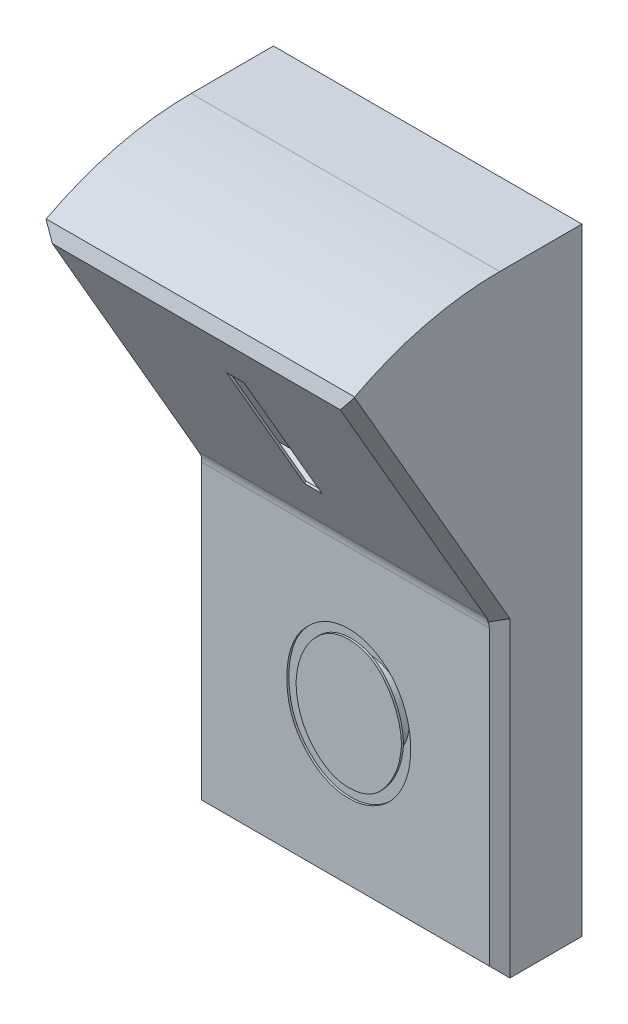
SolidWorks part; units mm, degrees
ref_plane "Plano frontal" through (0, 0, 0) normal (0, 0, 1) x (1, 0, 0)
ref_plane "Plano superior" through (0, 0, 0) normal (0, 1, 0) x (1, 0, 0)
ref_plane "Plano direito" through (0, 0, 0) normal (1, 0, 0) x (0, 0, -1)
sketch "Esboço1" plane through (0, 0, 0) normal (1, 0, 0) x (0, 0, -1)
  line L0 (0, 0) -> (0, 30)
  line L1 (0, 30) -> (-3.9988, 30)
  line L2 (0, 0) -> (-4, 0)
  line L3 (-4, 0) -> (-4, 15)
  line L6 (-11.5, 27.99) -> (-4, 15)
  arc A0 (-11.5, 27.99) -> (-3.9988, 30) centre (-3.9988, 14.9979) cw
extrude "Ressalto-extrusão1" add sketch "Esboço1" along normal blind 15
chamfer "Chanfro1" distance 0.5 angle 45 6 edges at (15, 21.495, 7.75) (7.5, 27.99, 11.5) (0, 21.495, 7.75) (0, 7.5, 4) (7.5, 0, 4) (15, 7.5, 4)
fillet "Filete1" radius 1 1 edges at (7.5, 15, 4)
sketch "Esboço2" plane through (0, 2.0181, -3.4953) normal (0, -0.5, 0.866) x (1, 0, 0)
  text T0 "l" font "Ebrima" height in points 28
sketch "Esboço4" plane through (0, 0, 4) normal (0, 0, 1) x (1, 0, 0)
  text T0 "O" font "Courier New" height in points 32
extrude "Corte-extrusão1" cut sketch "Esboço4" against normal blind 0.1
extrude "Corte-extrusão2" cut sketch "Esboço2" against normal blind 0.1
ref_plane "Plano1" through (0, 2.0681, -3.5819) normal (0, -0.5, 0.866) x (1, 0, 0)
sketch "Esboço5" plane through (0, 2.0681, -3.5819) normal (0, -0.5, 0.866) x (1, 0, 0)
  line L1 (12.5, 17.6012) -> (2.5, 17.6012)
  line L2 (12.5, 17.6012) -> (12.5, 27.2407)
  line L3 (12.5, 27.2407) -> (2.5, 27.2407)
  line L4 (2.5, 17.6012) -> (2.5, 27.2407)
  line L5 (12.5, 17.6012) -> (2.5, 27.2407) construction
  line L6 (12.5, 27.2407) -> (2.5, 17.6012) construction
  point P0 (7.5, 22.4209)
  point P5 (7.5, 22.4209)
extrude "Corte-extrusão3" cut sketch "Esboço5" against normal blind 1
ref_plane "Plano2" through (0, 0, 3.9) normal (0, 0, 1) x (1, 0, 0)
sketch "Esboço7" plane through (0, 0, 3.9) normal (0, 0, 1) x (1, 0, 0)
  line L1 (12.5, 2.616) -> (2.5, 2.616)
  line L2 (12.5, 2.616) -> (12.5, 12.616)
  line L3 (12.5, 12.616) -> (2.5, 12.616)
  line L4 (2.5, 2.616) -> (2.5, 12.616)
  line L5 (12.5, 2.616) -> (2.5, 12.616) construction
  line L6 (12.5, 12.616) -> (2.5, 2.616) construction
  circle A0 centre (7.5, 7.616) radius 2
  point P0 (7.5, 7.616)
extrude "Corte-extrusão4" cut sketch "Esboço7" against normal blind 1
